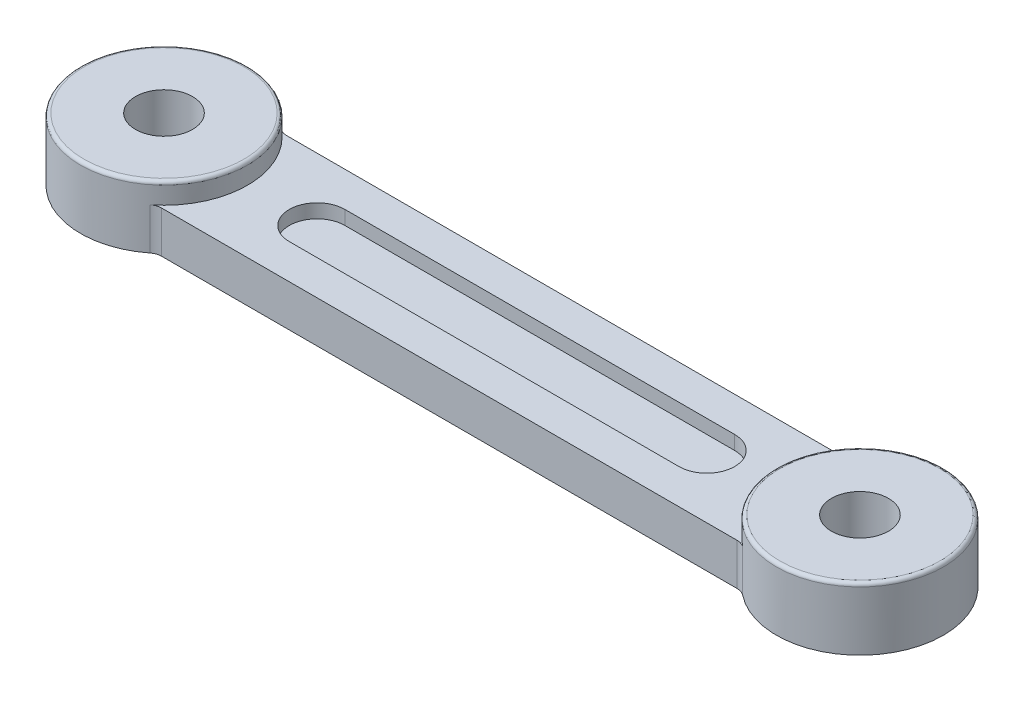
SolidWorks part; units mm, degrees
ref_plane "前视基准面" through (0, 0, 0) normal (0, 0, 1) x (1, 0, 0)
ref_plane "上视基准面" through (0, 0, 0) normal (0, 1, 0) x (1, 0, 0)
ref_plane "右视基准面" through (0, 0, 0) normal (1, 0, 0) x (0, 0, -1)
other "Configuration Table"
sketch "草图1" plane through (0, 0, 0) normal (0, 1, 0) x (1, 0, 0)
  line L0 (-50, 0) -> (50, 0) construction
  line L1 (-50, 9) -> (50, 9)
  line L2 (-50, -9) -> (50, -9)
  arc A0 (-50, 9) -> (-50, -9) centre (-50, 0) ccw
  arc A1 (50, -9) -> (50, 9) centre (50, 0) ccw
  point P2 (0, 0)
  dimension "D1" = 100
  dimension "D2" = 9
extrude "凸台-拉伸1" add sketch "草图1" along normal blind 6
sketch "草图2" plane through (0, 6, 0) normal (0, 1, 0) x (1, 0, 0)
  circle A0 centre (-50, 0) radius 12
  arc A1 (-50, 9) -> (-50, -9) centre (-50, 0) ccw construction
  circle A2 centre (50, 0) radius 12
  arc A3 (50, -9) -> (50, 9) centre (50, 0) ccw construction
  dimension "D1" = 24
  dimension "D2" = 24
extrude "凸台-拉伸2" add sketch "草图2" along normal blind 3
sketch "草图3" plane through (0, 9, 0) normal (0, 1, 0) x (1, 0, 0)
  circle A0 centre (-50, 0) radius 4.1
  circle A1 centre (-50, 0) radius 12 construction
  circle A2 centre (50, 0) radius 4.1
  circle A3 centre (50, 0) radius 12 construction
  dimension "D1" = 8.2
  dimension "D2" = 8.2
extrude "切除-拉伸1" cut sketch "草图3" against normal through all
sketch "草图4" plane through (0, 6, 0) normal (0, 1, 0) x (1, 0, 0)
  line L0 (-28, 0) -> (28, 0) construction
  line L1 (-28, 4) -> (28, 4)
  line L2 (-28, -4) -> (28, -4)
  arc A0 (-28, 4) -> (-28, -4) centre (-28, 0) ccw
  arc A1 (28, -4) -> (28, 4) centre (28, 0) ccw
  point P2 (0, 0)
  dimension "D1" = 56
  dimension "D2" = 4
extrude "切除-拉伸2" cut sketch "草图4" against normal blind 2
fillet "圆角1" radius 0.5 2 edges at (50, 9, 12) (-50, 9, 12)
sketch "草图5" plane through (0, 0, 0) normal (0, -1, 0) x (1, 0, 0)
  circle A0 centre (-50, 0) radius 12
  arc A1 (-50, 9) -> (-50, -9) centre (-50, 0) ccw construction
  circle A2 centre (50, 0) radius 12
  arc A3 (50, -9) -> (50, 9) centre (50, 0) ccw construction
  circle A4 centre (50, 0) radius 4.1 construction
  circle A5 centre (-50, 0) radius 4.1 construction
  circle A6 centre (50, 0) radius 4.1
  circle A7 centre (-50, 0) radius 4.1
  dimension "D1" = 24
  dimension "D2" = 24
extrude "凸台-拉伸3" add sketch "草图5" against normal blind 6
fillet "圆角2" radius 2 4 edges at (-42.0627, 3, -9) (42.0627, 3, -9) (42.0627, 3, 9) (-42.0627, 3, 9)
